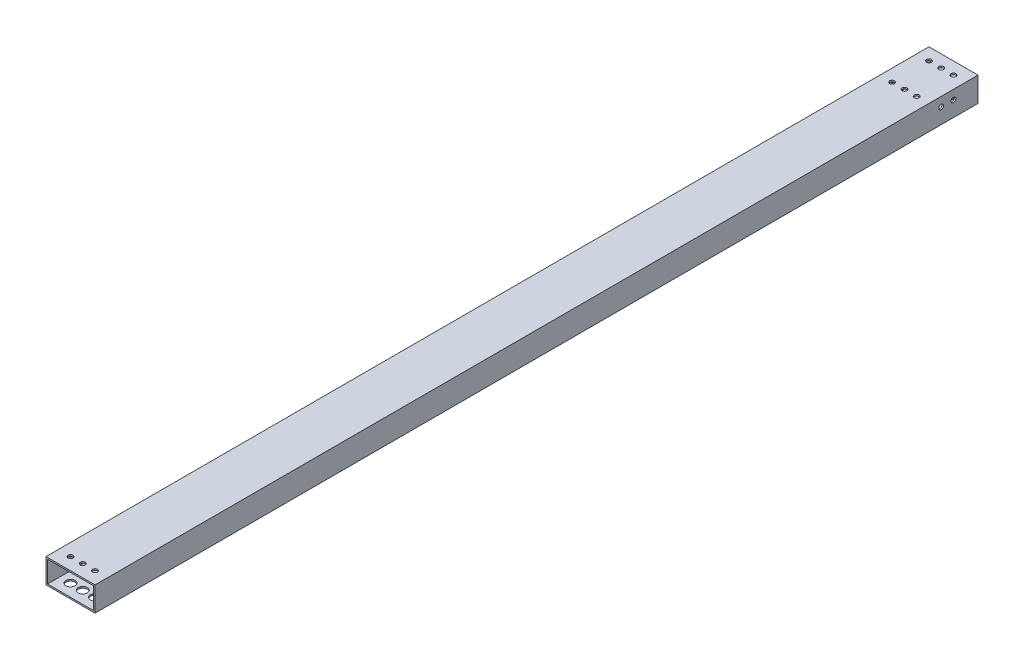
SolidWorks part; units mm, degrees
other "Markup1"
sketch "Sketch5" plane through (-25.4, -12.7, -457.2) normal (-0.35, -0.9329, -0.0852) x (-0.8023, 0.2515, 0.5413)
sketch "Sketch6" plane through (-25.4, -12.7, -457.2) normal (-0.35, -0.9329, -0.0852) x (-0.8023, 0.2515, 0.5413)
sketch "Sketch8" plane through (-25.4, -12.7, -457.2) normal (-0.35, -0.9329, -0.0852) x (-0.8023, 0.2515, 0.5413)
sketch "Sketch9" plane through (-25.4, -12.7, -457.2) normal (-0.35, -0.9329, -0.0852) x (-0.8023, 0.2515, 0.5413)
sketch "Sketch11" plane through (-25.4, -12.7, -457.2) normal (-0.35, -0.9329, -0.0852) x (-0.8023, 0.2515, 0.5413)
sketch "Sketch13" plane through (-25.4, -12.7, -457.2) normal (-0.35, -0.9329, -0.0852) x (-0.8023, 0.2515, 0.5413)
sketch "Sketch14" plane through (-25.4, -12.7, -457.2) normal (-0.35, -0.9329, -0.0852) x (-0.8023, 0.2515, 0.5413)
sketch "Sketch15" plane through (-25.4, -12.7, -457.2) normal (-0.35, -0.9329, -0.0852) x (-0.8023, 0.2515, 0.5413)
sketch "Sketch16" plane through (-25.4, -12.7, -457.2) normal (-0.35, -0.9329, -0.0852) x (-0.8023, 0.2515, 0.5413)
sketch "Sketch17" plane through (-25.4, -12.7, -457.2) normal (-0.35, -0.9329, -0.0852) x (-0.8023, 0.2515, 0.5413)
material "6061-T6 (SS)"
ref_plane "Front Plane" through (0, 0, 0) normal (0, 0, 1) x (1, 0, 0)
ref_plane "Top Plane" through (0, 0, 0) normal (0, 1, 0) x (1, 0, 0)
ref_plane "Right Plane" through (0, 0, 0) normal (1, 0, 0) x (0, 0, -1)
sketch "Sketch1" plane through (0, 0, 0) normal (0, 0, 1) x (1, 0, 0)
  line L0 (-23.8125, 11.1125) -> (23.8125, 11.1125)
  line L1 (-25.4, -12.7) -> (25.4, -12.7)
  line L2 (-25.4, -12.7) -> (-25.4, 12.7)
  line L3 (-25.4, 12.7) -> (25.4, 12.7)
  line L4 (25.4, -12.7) -> (25.4, 12.7)
  line L5 (-25.4, -12.7) -> (25.4, 12.7) construction
  line L6 (-25.4, 12.7) -> (25.4, -12.7) construction
  line L7 (23.8125, -11.1125) -> (23.8125, 11.1125)
  line L8 (-23.8125, -11.1125) -> (23.8125, -11.1125)
  line L9 (-23.8125, -11.1125) -> (-23.8125, 11.1125)
  point P0 (0, 0)
  dimension "D1" = 50.8
  dimension "D2" = 25.4
  dimension "D3" = 1.5875
extrude "Boss-Extrude1" add sketch "Sketch1" along normal mid plane 914.4
sketch "Sketch3" plane through (0, 12.7, 0) normal (0, 1, 0) x (1, 0, 0)
  line L2 (25.4, -457.2) -> (-25.4, -457.2) construction
  line L3 (25.4, 0) -> (-25.4, 0) construction
  line L4 (25.4, -457.2) -> (25.4, 457.2) construction
  line L5 (-25.4, -457.2) -> (-25.4, 457.2) construction
  circle A0 centre (0, -444.5) radius 2.5527
  circle A1 centre (12.7, -444.5) radius 2.5527
  circle A2 centre (-12.7, -444.5) radius 2.5527
  circle A3 centre (12.7, 444.5) radius 2.5527
  circle A4 centre (0, 444.5) radius 2.5527
  circle A5 centre (-12.7, 444.5) radius 2.5527
  dimension "D1" = 5.1054
  dimension "D2" = 12.7
  dimension "D3" = 12.7
  dimension "D4" = 12.7
extrude "Cut-Extrude2" cut sketch "Sketch3" against normal up to surface (1.5875 mm away) up to face at (0, 11.1125, 0)
sketch "Sketch4" plane through (0, -12.7, 0) normal (0, -1, 0) x (1, 0, 0)
  circle A0 centre (-12.7, 444.5) radius 2.5527 construction
  circle A1 centre (0, 444.5) radius 2.5527 construction
  circle A2 centre (12.7, 444.5) radius 2.5527 construction
  circle A3 centre (-12.7, 444.5) radius 2.5527
  circle A4 centre (0, 444.5) radius 2.5527
  circle A5 centre (12.7, 444.5) radius 2.5527
  circle A6 centre (-12.7, -444.5) radius 2.5527 construction
  circle A7 centre (0, -444.5) radius 2.5527 construction
  circle A8 centre (12.7, -444.5) radius 2.5527 construction
  circle A9 centre (-12.7, -444.5) radius 2.5527
  circle A10 centre (0, -444.5) radius 2.5527
  circle A11 centre (12.7, -444.5) radius 2.5527
  circle A12 centre (-12.7, 444.5) radius 4.7625
  circle A13 centre (0, 444.5) radius 4.7625
  circle A14 centre (12.7, 444.5) radius 4.7625
  circle A15 centre (-12.7, -444.5) radius 4.7625
  circle A16 centre (0, -444.5) radius 4.7625
  circle A17 centre (12.7, -444.5) radius 4.7625
  dimension "D1" = 9.525
  dimension "D2" = 9.525
extrude "Cut-Extrude4" cut sketch "Sketch4" against normal up to surface (1.5875 mm away) contours A12 A3 | A13 A4 | A4 | A3 | A5 | A14 A5 | A11 | A17 A11 | A16 A10 | A10 | A15 A9 | A9 region at (-12.7, -12.7, 444.5) region at (0, -12.7, 444.5) region at (12.7, -12.7, 444.5) region at (-12.7, -12.7, -444.5) region at (0, -12.7, -444.5) region at (12.7, -12.7, -444.5) region at (-17.3278, -12.7, 444.5) region at (-4.6278, -12.7, 444.5) region at (8.0722, -12.7, 444.5) region at (-17.3278, -12.7, -444.5) region at (-4.6278, -12.7, -444.5) region at (8.0722, -12.7, -444.5) up to face at (0, -11.1125, 0)
sketch "Sketch7" plane through (25.4, 0, 0) normal (1, 0, 0) x (0, 0, -1)
  line L1 (-457.2, 12.7) -> (457.2, 12.7) construction
  line L2 (0, 12.7) -> (0, -12.7) construction
  line L3 (-457.2, -12.7) -> (457.2, -12.7) construction
  line L5 (457.2, -12.7) -> (457.2, 12.7) construction
  circle A4 centre (406.4, 3.175) radius 2.4892
  circle A5 centre (419.1, 3.175) radius 2.4892
  circle A6 centre (431.8, 3.175) radius 2.4892
  circle A7 centre (444.5, 3.175) radius 2.4892
  dimension "D3" = 9.525
  dimension "D2" = 4.9784
  dimension "D1" = 12.7
  dimension "D4" = 12.7
  dimension "D5" = 12.7
  dimension "D6" = 12.7
extrude "Cut-Extrude5" cut sketch "Sketch7" against normal through all contours A5 | A6 region at (25.4, 3.175, -419.1) region at (25.4, 3.175, -431.8)
sketch "Sketch10" plane through (0, 12.7, 0) normal (0, 1, 0) x (1, 0, 0)
  line L0 (25.4, 457.2) -> (-25.4, 457.2) construction
  circle A0 centre (-12.7, 406.4) radius 2.5527
  circle A1 centre (0, 406.4) radius 2.5527
  circle A2 centre (12.7, 406.4) radius 2.5527
  dimension "D1" = 5.1054
  dimension "D2" = 12.7
  dimension "D3" = 12.7
  dimension "D4" = 50.8
extrude "Cut-Extrude6" cut sketch "Sketch10" against normal through all
